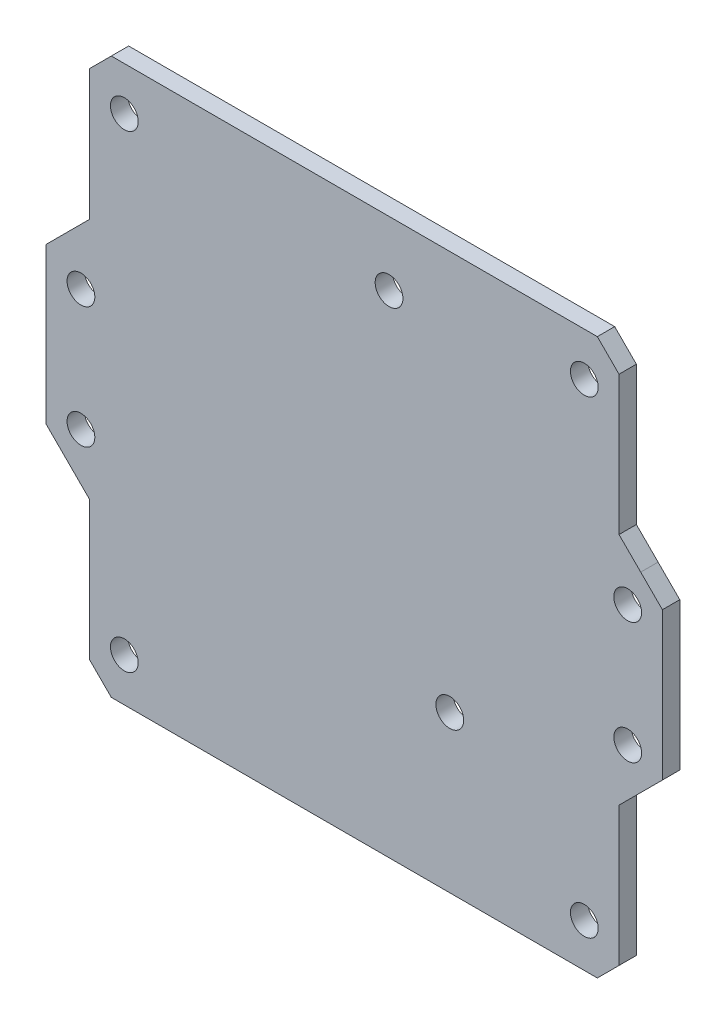
SolidWorks part; units mm, degrees
ref_plane "Front" through (0, 0, 0) normal (0, 0, 1) x (1, 0, 0)
ref_plane "Top" through (0, 0, 0) normal (0, 1, 0) x (1, 0, 0)
ref_plane "Right" through (0, 0, 0) normal (1, 0, 0) x (0, 0, -1)
sketch "草图1" plane through (0, 0, 0) normal (0, 0, 1) x (1, 0, 0)
  line L1 (-30, 41) -> (8, 41)
  line L2 (-30, 41) -> (-30, -13)
  line L3 (-30, -13) -> (8, -13)
  line L4 (8, 41) -> (8, -13)
  circle A0 centre (0, 0) radius 1.6
  circle A1 centre (-7, 38.6) radius 1.6
  dimension "D1" = 7
  dimension "D2" = 38.6
  dimension "D5" = 2.4
  dimension "D6" = 8
  dimension "D7" = 3.2
  dimension "D8" = 3.2
  dimension "D3" = 54
  dimension "D4" = 38
extrude "凸台-拉伸1" add sketch "草图1" along normal blind 2
sketch "草图2" plane through (0, 0, 0) normal (0, 0, 1) x (1, 0, 0)
  line L0 (8, 41) -> (-30, 41) construction
  line L5 (-33.5, 44) -> (11.5, 44)
  line L6 (-33.5, 44) -> (-33.5, -16)
  line L7 (-33.5, -16) -> (11.5, -16)
  line L8 (11.5, 44) -> (11.5, -16)
  line L9 (-30, 41) -> (-30, -13) construction
  point P4 (-11, 44)
  point P7 (-11, 41)
  point P8 (-33.5, 14)
  point P11 (-30, 14)
  dimension "D1" = 45
  dimension "D2" = 60
  dimension "D3" = 0
  dimension "D4" = 0
sketch "草图4" plane through (0, 0, 0) normal (0, 0, 1) x (1, 0, 0)
  line L1 (11.5, 44) -> (11.5, -16) construction
  line L2 (-33.5, 44) -> (11.5, 44) construction
  line L3 (-33.5, -16) -> (11.5, -16) construction
  line L6 (-33.88, 46) -> (19.5, 46)
  line L7 (19.5, 46) -> (19.5, 25)
  line L8 (19.5, 25) -> (24.5, 25)
  line L9 (24.5, 25) -> (24.5, 3)
  line L10 (24.5, 3) -> (19.5, 3)
  line L11 (19.5, 3) -> (19.5, -18)
  line L12 (19.5, -18) -> (-41.5, -18)
  line L13 (-41.5, -18) -> (-41.5, 2.1197)
  line L16 (-33.88, 46) -> (-41.5, 46)
  line L17 (-41.5, 46) -> (-41.5, 25.9601)
  line L18 (-41.5, 25.9601) -> (-46.5, 25.9601)
  line L19 (-46.5, 25.9601) -> (-46.5, 3)
  line L20 (-46.5, 3) -> (-41.5, 3)
  line L21 (-41.5, 3) -> (-41.5, 2.1197)
  circle A0 centre (-37.5, 41) radius 1.6
  circle A1 centre (15.5, -13) radius 1.6
  circle A2 centre (-37.5, -13) radius 1.6
  circle A3 centre (15.5, 41) radius 1.6
  circle A4 centre (-42.5, 21) radius 1.6
  circle A5 centre (20.5, 7) radius 1.6
  circle A7 centre (-42.5, 7) radius 1.6
  circle A8 centre (20.5, 21) radius 1.6
  circle A9 centre (-7, 38.6) radius 1.6
  circle A10 centre (0, 0) radius 1.6
  dimension "D2" = 4
  dimension "D3" = 3
  dimension "D4" = 3
  dimension "D5" = 0
  dimension "D6" = 0
  dimension "D7" = 0
  dimension "D8" = 0
  dimension "D9" = 5
  dimension "D10" = 5
  dimension "D11" = 20
  dimension "D12" = 20
  dimension "D13" = 0
  dimension "D14" = 0
  dimension "D15" = 0
  dimension "D16" = 0
  dimension "D19" = 4
  dimension "D18" = 4
  dimension "D17" = 4
  dimension "D28" = 3.2
  dimension "D29" = 3.2
  dimension "D20" = 5
  dimension "D21" = 4
  dimension "D22" = 4
  dimension "D23" = 4
  dimension "D24" = 4
  dimension "D25" = 4
  dimension "D26" = 4
  dimension "D27" = 2
extrude "凸台-拉伸2" add sketch "草图4" along normal blind 2
fillet "圆角1" radius 2.5 12 edges at (19.5, -18, 1) (19.5, 3, 1) (24.5, 3, 1) (24.5, 25, 1) (19.5, 25, 1) (19.5, 46, 1) (-41.5, -18, 1) (-41.5, 3, 1) (-46.5, 3, 1) (-41.5, 25.9601, 1) (-46.5, 25.9601, 1) (-41.5, 46, 1) profile chamfer
